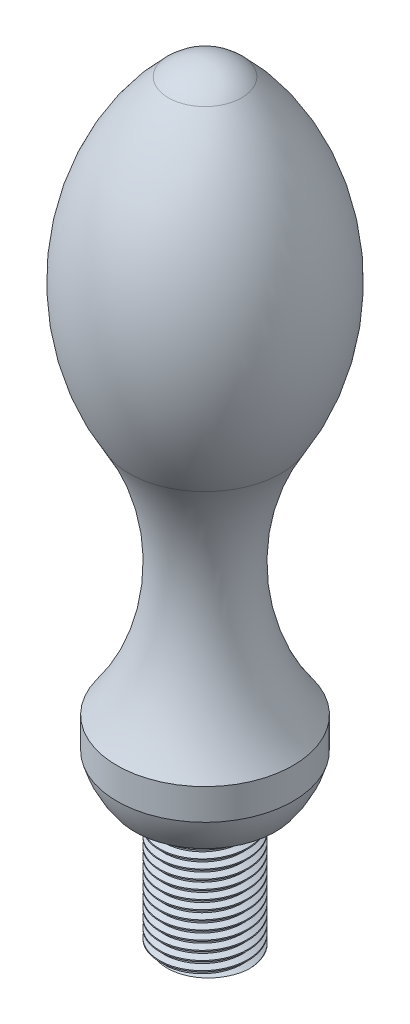
SolidWorks part; units mm, degrees
ref_plane "Front Plane" through (0, 0, 0) normal (0, 0, 1) x (1, 0, 0)
ref_plane "Top Plane" through (0, 0, 0) normal (0, 1, 0) x (1, 0, 0)
ref_plane "Right Plane" through (0, 0, 0) normal (1, 0, 0) x (0, 0, -1)
sketch "Sketch1" plane through (0, 0, 0) normal (0, 0, 1) x (1, 0, 0)
  line L0 (0, 0) -> (0, 87) construction
  line L1 (5, 0) -> (5, 15)
  line L2 (5, 15) -> (8, 15)
  line L3 (0, 87) -> (-7.4788, 87) construction
  line L4 (10, 19) -> (10, 22.5169)
  line L5 (5, 0) -> (0, 0)
  line L6 (0, 0) -> (0, 87)
  arc A0 (8, 15) -> (10, 19) centre (-0.6333, 21.8166) ccw
  arc A1 (0, 87) -> (4.165, 85.3189) centre (0, 81) cw
  arc A2 (4.165, 85.3189) -> (8.6298, 50.5789) centre (-15.2716, 65.164) cw
  arc A3 (8.6298, 50.5789) -> (10, 22.5169) centre (29.9702, 37.5565) ccw
  point P12 (5, 36.3372)
  point P19 (12.5, 68.7332)
  dimension "D4" = 16
  dimension "D5" = 11
  dimension "D8" = 6
  dimension "D9" = 28
  dimension "D10" = 10
  dimension "D11" = 25
  dimension "D12" = 25
  dimension "D1" = 87
  dimension "D2" = 10
  dimension "D3" = 15
  dimension "D6" = 4
  dimension "D7" = 20
revolve "Revolve1" add sketch "Sketch1" angle 360 about L6
thread "Thread1" pitch 1 method cut trim with start face yes trim with end face yes profile "Thread Profile1" start angle 0, offset 5, length 0, pitch 1, diameter 10
ref_plane "Plane1" through (5, -5, 0) normal (0, 0, 1) x (1, 0, 0)
sketch "Thread Profile1" plane through (5, -5, 0) normal (0, 0, 1) x (1, 0, 0)
  line L0 (0, 0) -> (0, 1) construction
  line L11 (0, 0) -> (0, 0.875)
  line L12 (0, 0.875) -> (-0.5413, 0.5625)
  line L13 (-0.5413, 0.5625) -> (-0.5413, 0.3125)
  line L15 (-0.5413, 0.3125) -> (0, 0)
  line L17 (-0.5413, 0.4375) -> (0, 0.4375) construction
  point P2 (0, 0)
  dimension "Pitch" = 1
  dimension "Profile_Angle" = 60
  dimension "Profile_Land" = 0.25
  dimension "Profile_Height" = 0.5413
